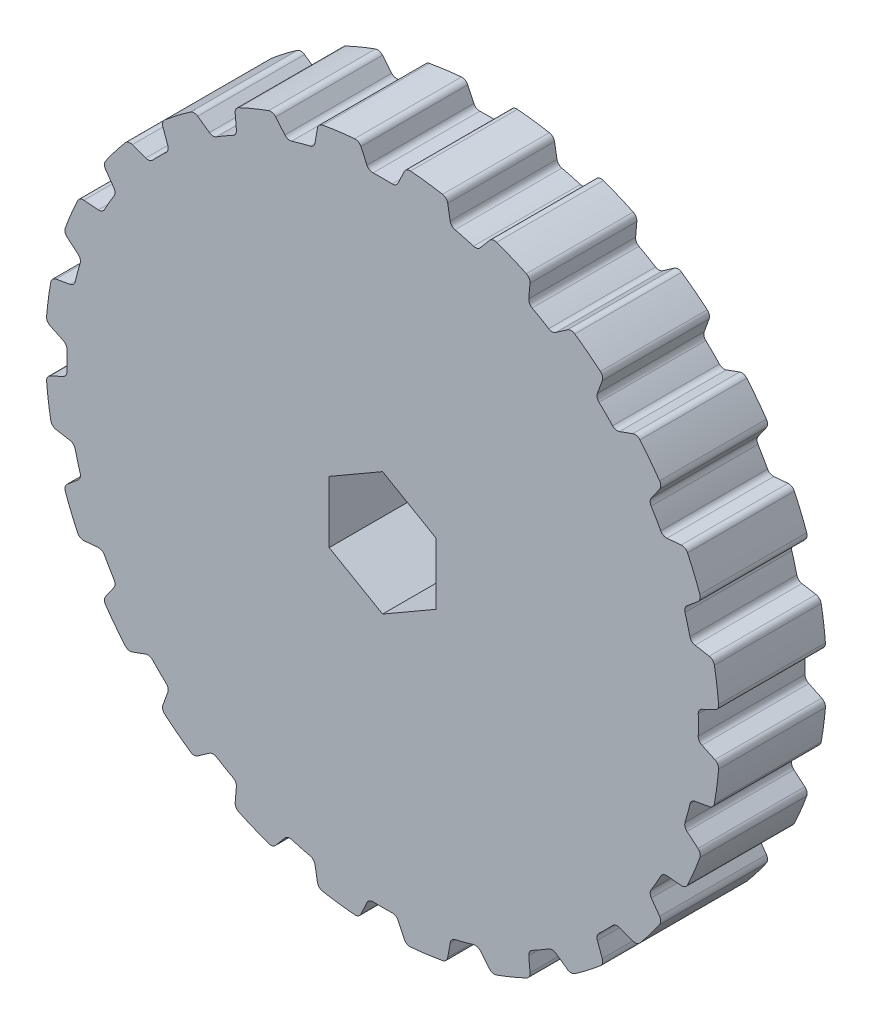
SolidWorks part; units mm, degrees
material "ABS"
ref_plane "Front Plane" through (0, 0, 0) normal (0, 0, 1) x (1, 0, 0)
ref_plane "Top Plane" through (0, 0, 0) normal (0, 1, 0) x (1, 0, 0)
ref_plane "Right Plane" through (0, 0, 0) normal (1, 0, 0) x (0, 0, -1)
sketch "Sketch3" plane through (0, 0, 0) normal (0, 0, 1) x (1, 0, 0)
  line L1 (0, 3.6662) -> (-3.175, 1.8331)
  line L2 (-3.175, 1.8331) -> (-3.175, -1.8331)
  line L3 (-3.175, -1.8331) -> (0, -3.6662)
  line L4 (0, -3.6662) -> (3.175, -1.8331)
  line L5 (3.175, -1.8331) -> (3.175, 1.8331)
  line L6 (3.175, 1.8331) -> (0, 3.6662)
  circle A0 centre (0, 0) radius 20.0392
  circle A1 centre (0, 0) radius 3.175 construction
  dimension "D1" = 40.0783
  dimension "D2" = 6.35
extrude "Boss-Extrude1" add sketch "Sketch3" along normal blind 6.35
sketch "Sketch4" plane through (0, 0, 6.35) normal (0, 0, 1) x (1, 0, 0)
  line L1 (-1.397, 19.9904) -> (0, 0) construction
  line L2 (0, 0) -> (1.397, 19.9904) construction
  line L3 (-1.397, 19.9904) -> (-0.8192, 18.7513)
  line L4 (1.397, 19.9904) -> (0.8192, 18.7513)
  circle A0 centre (0, 0) radius 18.7692 construction
  circle A1 centre (0, 0) radius 20.0392 construction
  arc A2 (-0.8192, 18.7513) -> (0.8192, 18.7513) centre (0, 0) cw
  arc A3 (-1.397, 19.9904) -> (1.397, 19.9904) centre (0, 0) cw
  circle A4 centre (0, 0) radius 20.0392 construction
  point P7 (0, 20.0392)
  circle M5 centre (0, 0) radius 20.0392
  dimension "D2" = 1.27
  dimension "D3" = 50
  dimension "D4" = 2.794
extrude "Cut-Extrude1" cut sketch "Sketch4" against normal through all contours L3 A2 L4 M5 region at (0, 19.4482, 6.35)
fillet "Fillet1" radius 0.381 4 edges at (-0.8192, 18.7513, 3.175) (-1.397, 19.9904, 3.175) (0.8192, 18.7513, 3.175) (1.397, 19.9904, 3.175)
sketch3d "3DSketch1"
  line L0 (0, 0, 0) -> (0, 0, -25.4) construction
  dimension "D1" = 25.4
ref_axis "Axis1" through (0, 0, 0) along (0, 0, -1)
pattern_circular "CirPattern1" count 24 over 360 about axis through (0, 0, 0) along (0, 0, -1) of "Fillet1", "Cut-Extrude1"
sketch "Sketch5" plane through (0, 0, 6.35) normal (0, 0, 1) x (1, 0, 0)
  line L0 (0, 20.0392) -> (0, 18.7692) construction
  line L1 (5.1865, 19.3564) -> (4.8578, 18.1296) construction
  arc A0 (0.5691, 18.7605) -> (-0.5691, 18.7605) centre (0, 0) ccw construction
  arc A1 (5.4053, 17.974) -> (4.3058, 18.2686) centre (0, 0) ccw construction
  arc A2 (-2.6156, 19.8677) -> (2.6156, 19.8677) centre (0, 0) cw construction
  arc A3 (-1.6625, 19.9701) -> (-3.5628, 19.7199) centre (0, 0) ccw construction
  arc A4 (3.5628, 19.7199) -> (1.6625, 19.9701) centre (0, 0) ccw construction
  arc A5 (2.6156, 19.8677) -> (7.6687, 18.5138) centre (0, 0) cw construction
  arc A6 (8.5453, 18.1258) -> (6.7745, 18.8593) centre (0, 0) ccw construction
  point P0 (0, 18.7692)
  point P1 (4.8578, 18.1296)
  point P19 (2.6156, 19.8677)
  point P25 (7.6687, 18.5138)
  point P28 (0, 19.4042)
  point P30 (5.0222, 18.743)
  dimension "D1" = 4.8997
  dimension "D2" = 5.0655
